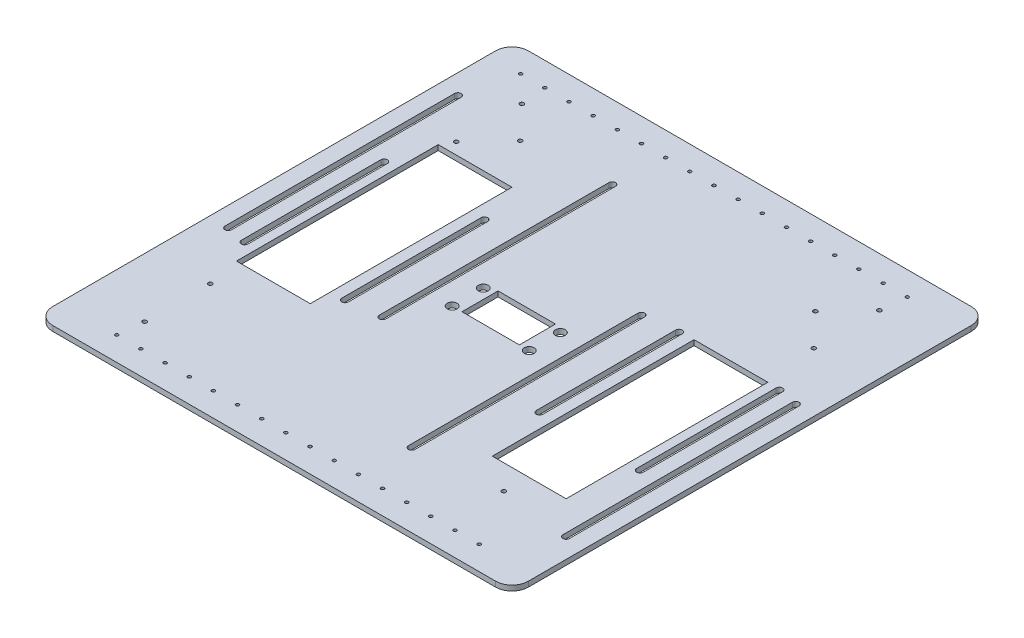
SolidWorks part; units mm, degrees
ref_plane "Front Plane" through (0, 0, 0) normal (0, 0, 1) x (1, 0, 0)
ref_plane "Top Plane" through (0, 0, 0) normal (0, 1, 0) x (1, 0, 0)
ref_plane "Right Plane" through (0, 0, 0) normal (1, 0, 0) x (0, 0, -1)
sketch "Sketch1" plane through (0, 0, 0) normal (0, 1, 0) x (1, 0, 0)
  line L0 (-145, 130.5) -> (145, 130.5) construction
  line L1 (145, -145) -> (-145, -145)
  line L2 (145, -145) -> (145, 145)
  line L3 (145, 145) -> (-145, 145)
  line L4 (-145, -145) -> (-145, 145)
  line L5 (145, -145) -> (-145, 145) construction
  line L6 (145, 145) -> (-145, -145) construction
  line L7 (-145, 116) -> (145, 116) construction
  line L8 (-145, 101.5) -> (145, 101.5) construction
  line L9 (-145, 87) -> (145, 87) construction
  line L10 (-145, 72.5) -> (145, 72.5) construction
  line L11 (-145, 58) -> (145, 58) construction
  line L12 (-145, 43.5) -> (145, 43.5) construction
  line L13 (-145, 29) -> (145, 29) construction
  line L14 (-145, 14.5) -> (145, 14.5) construction
  line L15 (-145, 0) -> (145, 0) construction
  line L16 (-145, -14.5) -> (145, -14.5) construction
  line L17 (-145, -29) -> (145, -29) construction
  line L18 (-145, -43.5) -> (145, -43.5) construction
  line L19 (-145, -58) -> (145, -58) construction
  line L20 (-145, -72.5) -> (145, -72.5) construction
  line L21 (-145, -87) -> (145, -87) construction
  line L22 (-145, -101.5) -> (145, -101.5) construction
  line L23 (-145, -116) -> (145, -116) construction
  line L24 (-145, -130.5) -> (145, -130.5) construction
  line L25 (-145, -145) -> (145, -145) construction
  point P0 (0, 0)
  dimension "D1" = 290
  dimension "D2" = 290
  dimension "D3" = 14.5
  dimension "D5" = 14.5
  dimension "D4" = 20
extrude "Base Plate" add sketch "Sketch1" along normal blind 3.175
hole_wizard "Caster Holes" positions "Sketch2" profile "Sketch3" hole size "Ø2.0" standard "ANSI Metric" end condition through all
sketch "Sketch2" plane through (0, 3.175, 0) normal (0, 1, 0) x (1, 0, 0)
  line L5 (0, -145) -> (0, 145) construction
  line L6 (145, 145) -> (-145, 145) construction
  line L8 (-145, 0) -> (145, 0) construction
  line L9 (-145, 0) -> (145, 0) construction
  line L10 (-145, 130.5) -> (145, 130.5) construction
  point P200 (-7.366, 130.5)
  point P217 (-22.098, 130.5)
  point P218 (-36.83, 130.5)
  point P219 (-51.562, 130.5)
  point P220 (-66.294, 130.5)
  point P221 (-81.026, 130.5)
  point P222 (-95.758, 130.5)
  point P223 (-110.49, 130.5)
  point P224 (110.49, 130.5)
  point P225 (95.758, 130.5)
  point P226 (81.026, 130.5)
  point P227 (66.294, 130.5)
  point P228 (51.562, 130.5)
  point P229 (36.83, 130.5)
  point P230 (22.098, 130.5)
  point P231 (7.366, 130.5)
  point P232 (7.366, -130.5)
  point P233 (22.098, -130.5)
  point P234 (36.83, -130.5)
  point P235 (51.562, -130.5)
  point P236 (66.294, -130.5)
  point P237 (81.026, -130.5)
  point P238 (95.758, -130.5)
  point P239 (110.49, -130.5)
  point P240 (-110.49, -130.5)
  point P241 (-95.758, -130.5)
  point P242 (-81.026, -130.5)
  point P243 (-66.294, -130.5)
  point P244 (-51.562, -130.5)
  point P245 (-36.83, -130.5)
  point P246 (-22.098, -130.5)
  point P247 (-7.366, -130.5)
  point P250 (-125.222, 130.5)
  dimension "D1" = 7.366
  dimension "D3" = 14.732
  dimension "D2" = 9
sketch "Sketch3" plane through (-125.222, 3.175, -130.5) normal (1, 0, 0) x (0, 0, 1)
  line L0 (0, 0) -> (0, 3.175)
  line L1 (0, 3.175) -> (1, 3.175)
  line L2 (1, 3.175) -> (1, 0)
  line L5 (1, 0) -> (0, 0)
  line L11 (0, -6.35) -> (0, 107.95) construction
  dimension "Thru Hole Dia." = 2
  dimension "Thru Hole Depth" = 3.175
fillet "Fillet1" radius 10 4 edges at (145, 1.5875, 145) (-145, 1.5875, 145) (145, 1.5875, -145) (-145, 1.5875, -145)
sketch "Sketch4" plane through (0, 0, 0) normal (0, -1, 0) x (1, 0, 0)
  line L0 (145, 0) -> (-145, 0) construction
  line L1 (-145, -135) -> (-145, 135) construction
  line L2 (0, -145) -> (0, 145) construction
  line L3 (-135, 145) -> (135, 145) construction
  point P6 (0, 0)
  point P12 (0, 0)
sketch "Sketch5" plane through (0, 3.175, 0) normal (0, 1, 0) x (1, 0, 0)
  line L0 (0, 145) -> (0, -145) construction
  line L1 (145, 0) -> (-145, 0) construction
  line L2 (0, 145) -> (0, -145) construction
  line L4 (-17.5, -13) -> (17.5, -13)
  line L5 (-17.5, -13) -> (-17.5, 9)
  line L6 (-17.5, 9) -> (17.5, 9)
  line L7 (17.5, -13) -> (17.5, 9)
  line L8 (-17.5, -13) -> (17.5, 9) construction
  line L9 (-17.5, 9) -> (17.5, -13) construction
  circle A0 centre (-23.5, 6) radius 3
  circle A2 centre (-23.5, -13) radius 3
  circle A3 centre (23.5, 6) radius 3
  circle A4 centre (23.5, -13) radius 3
  point P13 (0, -2)
  dimension "D1" = 6
  dimension "D2" = 23.5
  dimension "D3" = 6
  dimension "D4" = 19
  dimension "D5" = 6
  dimension "D6" = 6
extrude "Reflect Holes" cut sketch "Sketch5" against normal up to surface (3.175 mm away) up to face at (-7.366, 0, -129.5)
sketch "Sketch6" plane through (0, 3.175, 0) normal (0, 1, 0) x (1, 0, 0)
  line L0 (-133, 145) -> (-133, -145) construction
  line L1 (135, 145) -> (-135, 145) construction
  line L2 (-135, -145) -> (135, -145) construction
  line L3 (-145, 135) -> (-145, -135) construction
  line L4 (-133, 100) -> (-133, -40) construction
  line L5 (-131, 100) -> (-131, -40)
  line L6 (-135, 100) -> (-135, -40)
  line L7 (-38.9, 100) -> (-38.9, -40) construction
  line L8 (-36.9, 100) -> (-36.9, -40)
  line L9 (-40.9, 100) -> (-40.9, -40)
  line L10 (-120.5, 42.5) -> (-120.5, -42.5) construction
  line L11 (-118.5, 42.5) -> (-118.5, -42.5)
  line L12 (-122.5, 42.5) -> (-122.5, -42.5)
  line L13 (-59.3, 42.5) -> (-59.3, -42.5) construction
  line L14 (-57.3, 42.5) -> (-57.3, -42.5)
  line L15 (-61.3, 42.5) -> (-61.3, -42.5)
  line L16 (145, 0) -> (-145, 0) construction
  line L17 (0, -145) -> (0, 145) construction
  line L18 (38.9, 100) -> (38.9, -40) construction
  line L19 (36.9, 100) -> (36.9, -40) construction
  line L20 (40.9, 100) -> (40.9, -40) construction
  line L21 (59.3, 42.5) -> (59.3, -42.5) construction
  line L22 (57.3, 42.5) -> (57.3, -42.5)
  line L23 (61.3, 42.5) -> (61.3, -42.5)
  line L24 (120.5, 42.5) -> (120.5, -42.5) construction
  line L25 (118.5, 42.5) -> (118.5, -42.5)
  line L26 (122.5, 42.5) -> (122.5, -42.5)
  line L27 (133, 100) -> (133, -40) construction
  line L28 (131, 100) -> (131, -40) construction
  line L29 (135, 100) -> (135, -40) construction
  line L30 (133, -100) -> (133, 40) construction
  line L31 (131, -100) -> (131, 40)
  line L32 (135, -100) -> (135, 40)
  line L33 (38.9, -100) -> (38.9, 40) construction
  line L34 (36.9, -100) -> (36.9, 40)
  line L35 (40.9, -100) -> (40.9, 40)
  arc A0 (-131, 100) -> (-135, 100) centre (-133, 100) ccw
  arc A1 (-135, -40) -> (-131, -40) centre (-133, -40) ccw
  arc A4 (-36.9, 100) -> (-40.9, 100) centre (-38.9, 100) ccw
  arc A5 (-40.9, -40) -> (-36.9, -40) centre (-38.9, -40) ccw
  arc A6 (-118.5, 42.5) -> (-122.5, 42.5) centre (-120.5, 42.5) ccw
  arc A7 (-122.5, -42.5) -> (-118.5, -42.5) centre (-120.5, -42.5) ccw
  arc A8 (-57.3, 42.5) -> (-61.3, 42.5) centre (-59.3, 42.5) ccw
  arc A9 (-61.3, -42.5) -> (-57.3, -42.5) centre (-59.3, -42.5) ccw
  arc A10 (36.9, 100) -> (40.9, 100) centre (38.9, 100) cw construction
  arc A11 (40.9, -40) -> (36.9, -40) centre (38.9, -40) cw construction
  arc A12 (57.3, 42.5) -> (61.3, 42.5) centre (59.3, 42.5) cw
  arc A13 (61.3, -42.5) -> (57.3, -42.5) centre (59.3, -42.5) cw
  arc A14 (118.5, 42.5) -> (122.5, 42.5) centre (120.5, 42.5) cw
  arc A15 (122.5, -42.5) -> (118.5, -42.5) centre (120.5, -42.5) cw
  arc A16 (131, 100) -> (135, 100) centre (133, 100) cw construction
  arc A17 (135, -40) -> (131, -40) centre (133, -40) cw construction
  arc A18 (131, -100) -> (135, -100) centre (133, -100) ccw
  arc A19 (135, 40) -> (131, 40) centre (133, 40) ccw
  arc A20 (36.9, -100) -> (40.9, -100) centre (38.9, -100) ccw
  arc A21 (40.9, 40) -> (36.9, 40) centre (38.9, 40) ccw
  point P10 (-133, 30)
  point P15 (-38.9, 30)
  point P27 (-120.5, 0)
  point P34 (-59.3, 0)
  point P44 (0, 0)
  point P46 (0, 0)
  point P48 (38.9, 30)
  point P55 (59.3, 0)
  point P62 (120.5, 0)
  point P69 (133, 30)
  point P76 (133, -30)
  point P83 (38.9, -30)
  dimension "D3" = 2
  dimension "D6" = 2
  dimension "D1" = 12
  dimension "D2" = 140
  dimension "D4" = 94.1
  dimension "D5" = 12.5
  dimension "D7" = 85
  dimension "D8" = 61.2
  dimension "D9" = 45
extrude "bearing slots" cut sketch "Sketch6" against normal up to surface (3.175 mm away) up to face at (23.5, 0, -3)
sketch "Sketch7" plane through (0, 3.175, 0) normal (0, 1, 0) x (1, 0, 0)
  line L0 (-145, 135) -> (-145, -135) construction
  line L9 (-113, 43) -> (-68, 43)
  line L10 (-113, 43) -> (-113, -55)
  line L11 (-113, -55) -> (-68, -55)
  line L12 (-68, 43) -> (-68, -55)
  point P9 (-68, -6)
  dimension "D2" = 98
  dimension "D1" = 45
  dimension "D3" = 32
  dimension "D4" = 6
extrude "wheel slots" cut sketch "Sketch7" against normal up to surface (3.175 mm away) up to face at (-133, 0, -30)
mirror "Mirror2" about plane through (0, 0, 0) normal (1, 0, 0) of "wheel slots"
sketch "Sketch9" plane through (0, 3.175, 0) normal (0, 1, 0) x (1, 0, 0)
  line L0 (-109, -145) -> (-109, 145) construction
  line L1 (135, 145) -> (-135, 145) construction
  line L2 (-145, 135) -> (-145, -135) construction
  line L3 (-135, -145) -> (135, -145) construction
  line L4 (90, -145) -> (90, 145) construction
  line L5 (145, -135) -> (145, 135) construction
  point P0 (-109, -75)
  point P1 (-109, -115)
  point P2 (90, -95)
  point P3 (-18.53, 6)
  point P8 (-109, 0)
  point P10 (0, 0)
  point P15 (90, -95.6794)
  point P21 (90, 0)
  dimension "D1" = 36
  dimension "D2" = 70
  dimension "D3" = 30
  dimension "D4" = 55
  dimension "D5" = 50
hole_wizard "#40 (0.098) Diameter Hole1" positions "Sketch10" profile "Sketch11" hole size "#40" standard "ANSI Inch" end condition through all
sketch "Sketch10" plane through (0, 3.175, 0) normal (0, 1, 0) x (1, 0, 0)
  line L0 (145, 0) -> (-145, 0) construction
  line L1 (-145, 135) -> (-145, -135) construction
  line L2 (0, -145) -> (0, 145) construction
  line L3 (135, 145) -> (-135, 145) construction
  line L4 (145, -145) -> (-145, 145) construction
  point P0 (-109, -75)
  point P3 (-109, -115)
  point P6 (90, -95)
  point P56 (0, 0)
  point P105 (0, 0)
  point P230 (0, 0)
  point P231 (90, 95)
  point P232 (-109, 115)
  point P233 (-109, 75)
  point P235 (-90, 95)
  point P236 (109, 75)
  point P237 (109, 115)
  dimension "D1" = 45
sketch "Sketch11" plane through (-109, 3.175, 75) normal (1, 0, 0) x (0, 0, 1)
  line L0 (0, 0) -> (0, 3.175)
  line L1 (0, 3.175) -> (1.2446, 3.175)
  line L2 (1.2446, 3.175) -> (1.2446, 0)
  line L5 (1.2446, 0) -> (0, 0)
  line L11 (0, -6.35) -> (0, 107.95) construction
  dimension "Thru Hole Dia." = 2.4892
  dimension "Thru Hole Depth" = 3.175
sketch "Sketch12" plane through (0, 3.175, 0) normal (0, 1, 0) x (1, 0, 0)
  line L10 (-68, 43) -> (-68, -55) construction
  line L11 (-113, 43) -> (-68, 43)
  line L12 (-113, 43) -> (-113, 68)
  line L13 (-113, 68) -> (-68, 68)
  line L14 (-68, 43) -> (-68, 68)
  line L15 (68, -55) -> (113, -55)
  line L16 (68, -55) -> (68, -80)
  line L17 (68, -80) -> (113, -80)
  line L18 (113, -55) -> (113, -80)
  line L19 (113, 43) -> (113, -55) construction
  dimension "D1" = 25
  dimension "D2" = 25
extrude "Cut-Extrude4" cut sketch "Sketch12" against normal up to surface (3.175 mm away) up to face at (-109, 0, 76.2446)
